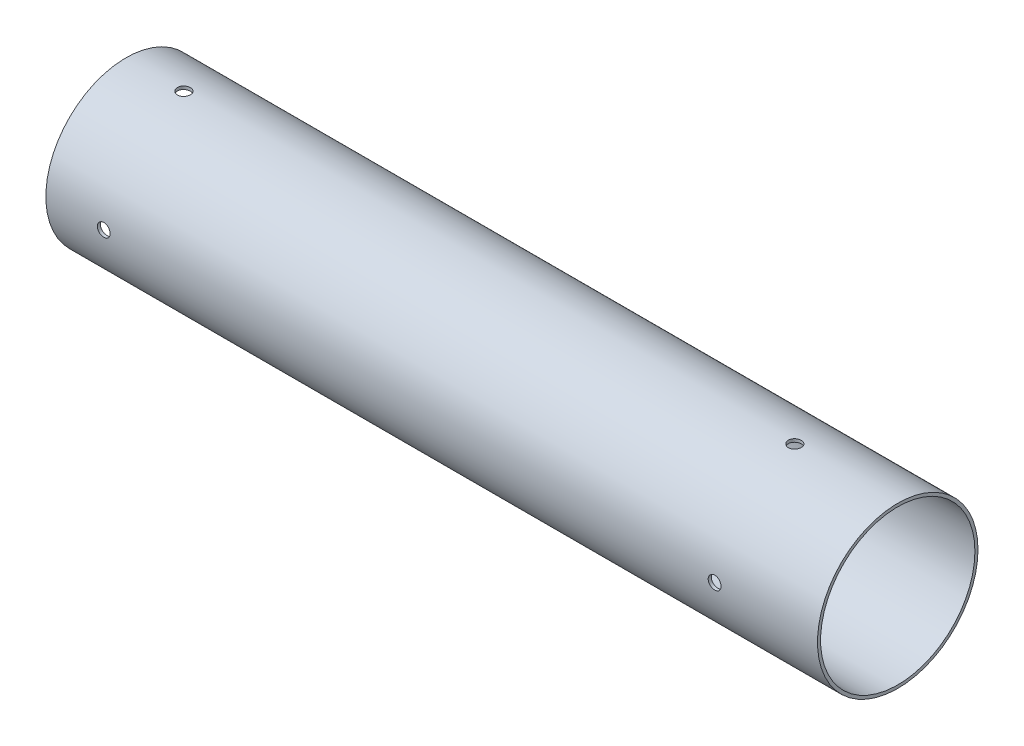
SolidWorks part; units mm, degrees
ref_plane "Front Plane" through (0, 0, 0) normal (1, 0, 0) x (0, 1, 0)
ref_plane "Top Plane" through (0, 0, 0) normal (0, 0, 1) x (0, 1, 0)
ref_plane "Right Plane" through (0, 0, 0) normal (0, 1, 0) x (-1, 0, 0)
sketch "Sketch1" plane through (0, 0, 0) normal (1, 0, 0) x (0, 1, 0)
  circle A0 centre (0, 0) radius 39.624
  circle A1 centre (0, 0) radius 38.1
  dimension "D1" = 79.248
  dimension "D2" = 76.2
extrude "Boss-Extrude1" add sketch "Sketch1" along normal blind 381
sketch "Sketch2" plane through (0, 0, 0) normal (0, 1, 0) x (-1, 0, 0)
  line L0 (-381, 39.624) -> (-381, -39.624) construction
  line L1 (-330.2, 0) -> (-381, 0) construction
  circle A0 centre (-330.2, 0) radius 3.175
  dimension "D1" = 6.35
  dimension "D2" = 50.8
extrude "Cut-Extrude1" cut sketch "Sketch2" along normal through all
pattern_circular "CirPattern1" count 4 over 360 about axis through (381, 0, 0) along (-1, 0, 0) of "Cut-Extrude1"
sketch "Sketch3" plane through (0, 0, 0) normal (0, 1, 0) x (-1, 0, 0)
  circle A0 centre (-28.575, 0) radius 3.175
  dimension "D1" = 6.35
  dimension "D2" = 28.575
extrude "Cut-Extrude2" cut sketch "Sketch3" along normal through all
pattern_circular "CirPattern2" count 4 over 360 about axis through (381, 0, 0) along (-1, 0, 0) of "Cut-Extrude2"
